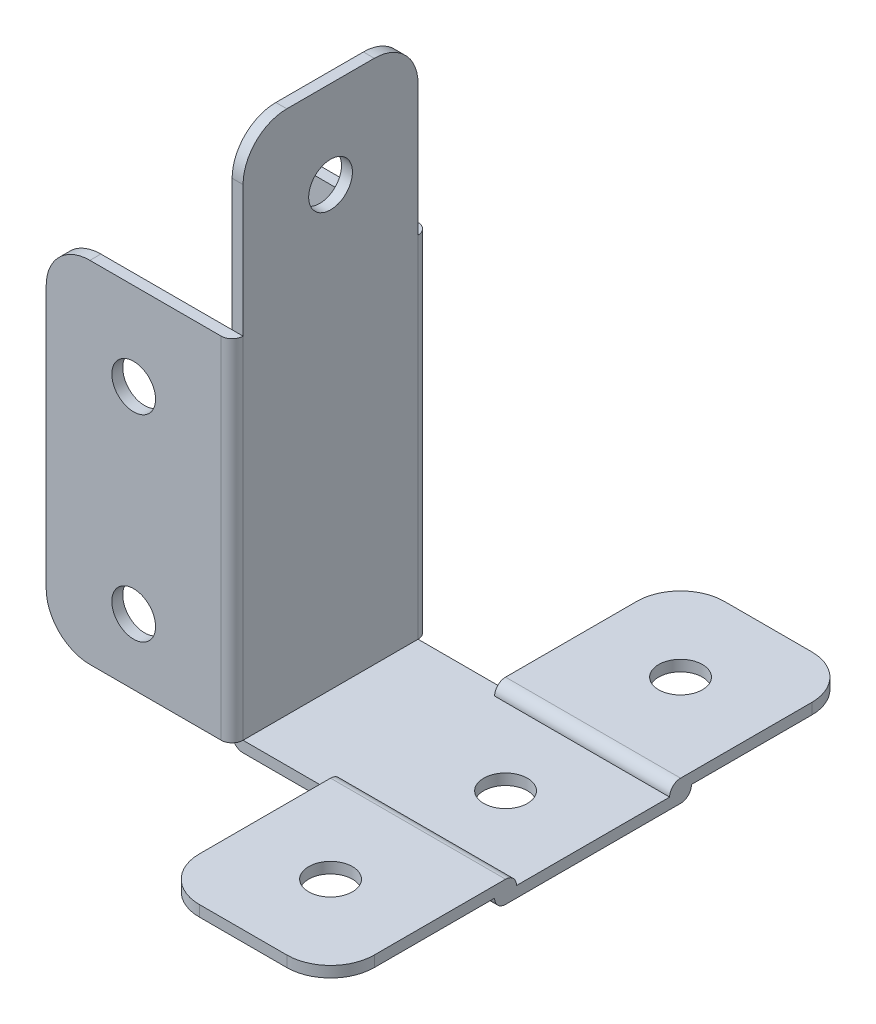
SolidWorks part; units mm, degrees
ref_plane "Front Plane" through (0, 0, 0) normal (0, 0, 1) x (1, 0, 0)
ref_plane "Top Plane" through (0, 0, 0) normal (0, 1, 0) x (1, 0, 0)
ref_plane "Right Plane" through (0, 0, 0) normal (1, 0, 0) x (0, 0, -1)
sketch "Sketch1" plane through (0, 0, 0) normal (0, 0, 1) x (1, 0, 0)
  line L0 (0, 0) -> (-25.4, 0)
  line L1 (-25.4, 0) -> (-25.4, 50.8)
  line L2 (-25.4, 50.8) -> (0, 50.8)
  line L3 (0, 50.8) -> (0, 0)
  line L4 (-12.7, 50.8) -> (-12.7, 0) construction
  circle A0 centre (-12.7, 38.1) radius 3.175
  circle A1 centre (-12.7, 9.525) radius 3.175
  dimension "D5" = 6.35
  dimension "D1" = 12.7
  dimension "D2" = 28.575
  dimension "D3" = 9.525
  dimension "D4" = 25.4
extrude "Boss-Extrude1" add sketch "Sketch1" along normal blind 1.5875
extrude "Boss-Extrude2" add sketch "Sketch1<2>" against normal blind 1.5875 from offset 25.4 separate body offset against normal yes
sketch "Sketch1<2>" plane through (0, 0, 0) normal (0, 0, 1) x (1, 0, 0) same geometry as "Sketch1"
sketch "Sketch3" plane through (0, 0, 0) normal (1, 0, 0) x (0, 0, -1)
  line L0 (25.4, 76.2) -> (0, 50.8) construction
  line L1 (25.4, 50.8) -> (0, 50.8) construction
  line L2 (25.4, 50.8) -> (25.4, 0)
  line L3 (25.4, 0) -> (0, 0)
  line L4 (0, 50.8) -> (0, 0)
  line L5 (25.4, 50.8) -> (0, 50.8) construction
  line L6 (25.4, 50.8) -> (25.4, 76.2)
  line L7 (25.4, 76.2) -> (0, 76.2)
  line L8 (0, 50.8) -> (0, 76.2)
  circle A0 centre (12.7, 63.5) radius 3.175
  dimension "D2" = 6.35
  dimension "D1" = 25.4
extrude "Boss-Extrude3" add sketch "Sketch3" along normal blind 1.5875 separate body
sketch "Sketch4" plane through (0, 0, 0) normal (0, 1, 0) x (1, 0, 0)
  line L1 (14.2875, -50.8) -> (39.6875, -50.8) construction
  line L3 (39.6875, 50.8) -> (14.2875, 50.8)
  line L4 (14.2875, 50.8) -> (14.2875, 25.4)
  line L5 (14.2875, 25.4) -> (14.2875, 0)
  line L6 (14.2875, 25.4) -> (39.6875, 25.4)
  line L7 (39.6875, 50.8) -> (39.6875, 25.4)
  line L8 (14.2875, -25.4) -> (39.6875, -25.4)
  line L9 (26.9875, -50.8) -> (26.9875, 50.8) construction
  line L10 (39.6875, -25.4) -> (39.6875, -50.8) construction
  line L11 (14.2875, 0) -> (14.2875, -25.4)
  line L12 (14.2875, -50.8) -> (14.2875, -25.4) construction
  line L13 (39.6875, -25.4) -> (39.6875, 25.4)
  line L14 (1.5875, 25.4) -> (14.2875, 25.4)
  line L15 (1.5875, 0) -> (14.2875, 0)
  line L16 (1.5875, 25.4) -> (1.5875, 0)
  line L17 (14.2875, 0) -> (39.6875, 0)
  circle A0 centre (26.9875, 12.7) radius 3.175
  circle A1 centre (26.9875, -12.7) radius 3.175
  circle A2 centre (26.9875, -38.1) radius 3.175 construction
  circle A3 centre (26.9875, 38.1) radius 3.175
  point P24 (39.6875, -4.6967)
  point P27 (0, 0)
  dimension "D2" = 6.35
  dimension "D1" = 12.7
  dimension "D3" = 12.7
  dimension "D4" = 25.4
  dimension "D5" = 12.7
  dimension "D6" = 12.7
  dimension "D7" = 12.7
  dimension "D8" = 12.7
  dimension "D9" = 25.4
  dimension "D10" = 12.7
extrude "Boss-Extrude4" add sketch "Sketch4" against normal blind 1.5875 separate body contours L14 L16 L15 L5 | L5 L17 L13 L6 A0 region at (39.3283, 0, -12.7) region at (7.9375, 0, -12.7)
sketch "Sketch6" plane through (0, 0, 0) normal (1, 0, 0) x (0, 0, -1)
  line L4 (0, 0) -> (0, 50.8)
  line L5 (0, 50.8) -> (-1.5875, 50.8)
  line L6 (-1.5875, 50.8) -> (-1.5875, 0)
  line L7 (-1.5875, 0) -> (0, 0)
  line L8 (0, 0) -> (0, 50.8)
  line L9 (0, 50.8) -> (-1.5875, 50.8)
  line L10 (-1.5875, 50.8) -> (-1.5875, 0)
  line L11 (-1.5875, 0) -> (0, 0)
  dimension "D1" = 0
revolve "Revolve1" add sketch "Sketch6" angle 90 about L8
sketch "Sketch7" plane through (0, 0, 0) normal (1, 0, 0) x (0, 0, -1)
  line L4 (25.4, 50.8) -> (25.4, 0)
  line L5 (25.4, 0) -> (26.9875, 0)
  line L6 (26.9875, 0) -> (26.9875, 50.8)
  line L7 (26.9875, 50.8) -> (25.4, 50.8)
  line L8 (25.4, 50.8) -> (25.4, 0)
  line L9 (25.4, 0) -> (26.9875, 0)
  line L10 (26.9875, 0) -> (26.9875, 50.8)
  line L11 (26.9875, 50.8) -> (25.4, 50.8)
  dimension "D1" = 0
revolve "Revolve2" add sketch "Sketch7" angle 90 about L8
sketch "Sketch8" plane through (1.5875, 0, 0) normal (-1, 0, 0) x (0, 0, 1)
  line L4 (0, 0) -> (-25.4, 0)
  line L5 (-25.4, 0) -> (-25.4, -1.5875)
  line L7 (0, -1.5875) -> (0, 0)
  line L9 (-25.4, 0) -> (-25.4, -1.5875)
  line L11 (0, -1.5875) -> (0, 0)
  line L14 (0, 0) -> (-25.4, 0)
  line L16 (-25.4, -1.5875) -> (0, -1.5875)
  line L17 (-25.4, -1.5875) -> (0, -1.5875)
  dimension "D1" = 0
revolve "Revolve3" add sketch "Sketch8" angle 90 about L14
sketch "Sketch9" plane through (0, 0, 0) normal (0, 1, 0) x (1, 0, 0)
  line L0 (14.2875, 25.4) -> (14.2875, 50.8)
  line L1 (14.2875, 50.8) -> (39.6875, 50.8)
  line L2 (39.6875, 50.8) -> (39.6875, 25.4)
  line L3 (39.6875, 25.4) -> (14.2875, 25.4)
  line L4 (14.2875, 0) -> (39.6875, 0)
  line L5 (39.6875, -25.4) -> (39.6875, 25.4) construction
  line L6 (39.6875, 0) -> (39.6875, -25.4)
  line L8 (39.6875, -25.4) -> (14.2875, -25.4)
  line L10 (14.2875, -25.4) -> (14.2875, 0)
  line L11 (26.9875, -50.8) -> (26.9875, 50.8) construction
  circle A0 centre (26.9875, 38.1) radius 3.175 construction
  circle A1 centre (26.9875, -12.7) radius 3.175 construction
  circle A2 centre (26.9875, 38.1) radius 3.175
  circle A3 centre (26.9875, -12.7) radius 3.175
  point P8 (26.9875, 34.925)
  point P11 (26.9875, -9.525)
extrude "Boss-Extrude5" add sketch "Sketch9" along normal blind 1.5875 contours L10 L8 L6 L4 A3 | L3 L2 L1 L0 A2 region at (14.6467, 0, -38.1) region at (26.9875, 0, 0.3592)
sketch "Sketch12" plane through (0, 0, -25.4) normal (0, 0, 1) x (1, 0, 0)
  line L4 (14.2875, 0) -> (39.6875, 0)
  line L5 (39.6875, 0) -> (39.6875, 1.5875)
  line L6 (39.6875, 1.5875) -> (14.2875, 1.5875)
  line L7 (14.2875, 1.5875) -> (14.2875, 0)
  line L8 (14.2875, 0) -> (39.6875, 0)
  line L9 (39.6875, 0) -> (39.6875, 1.5875)
  line L10 (39.6875, 1.5875) -> (14.2875, 1.5875)
  line L11 (14.2875, 1.5875) -> (14.2875, 0)
  dimension "D1" = 0
revolve "Revolve6" add sketch "Sketch12" angle 360 about L8
sketch "Sketch13" plane through (0, 0, 0) normal (0, 0, -1) x (-1, 0, 0)
  line L8 (-39.6875, 0) -> (-14.2875, 0)
  line L9 (-14.2875, 0) -> (-14.2875, 1.5875)
  line L10 (-14.2875, 1.5875) -> (-39.6875, 1.5875)
  line L11 (-39.6875, 1.5875) -> (-39.6875, 0)
  line L12 (-39.6875, 0) -> (-14.2875, 0)
  line L13 (-14.2875, 0) -> (-14.2875, 1.5875)
  line L14 (-14.2875, 1.5875) -> (-39.6875, 1.5875)
  line L15 (-39.6875, 1.5875) -> (-39.6875, 0)
  dimension "D1" = 0
revolve "Revolve7" add sketch "Sketch13" angle 360 about L12
fillet "Fillet6" radius 6.35 10 edges at (14.2875, 0.7937, -50.8) (39.6875, 0.7937, -50.8) (14.2875, 0.7937, 25.4) (39.6875, 0.7937, 25.4) (-25.4, 0, 0.7937) (-25.4, 0, -26.1937) (-25.4, 50.8, 0.7937) (-25.4, 50.8, -26.1937) (0.7937, 76.2, 0) (0.7937, 76.2, -25.4)
